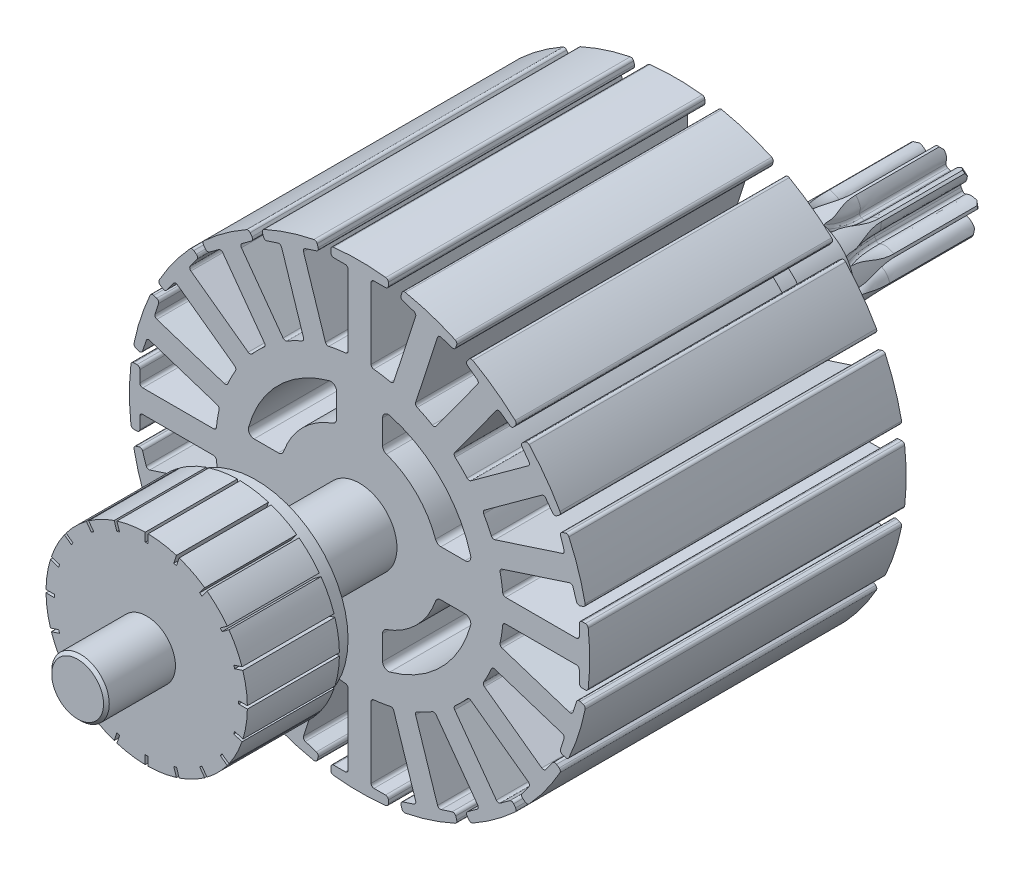
SolidWorks part; units mm, degrees
ref_plane "Plan de face" through (0, 0, 0) normal (0, 0, 1) x (1, 0, 0)
ref_plane "Plan de dessus" through (0, 0, 0) normal (0, 1, 0) x (1, 0, 0)
ref_plane "Plan de droite" through (0, 0, 0) normal (1, 0, 0) x (0, 0, -1)
sketch "Esquisse1" plane through (0, 0, 0) normal (0, 0, 1) x (1, 0, 0)
  line L0 (0, 0) -> (0, 10.3983) construction
  line L1 (0, 0) -> (3.7078, 10.1871) construction
  line L2 (0, 0) -> (2.253, 11.5906) construction
  line L3 (0, 0) -> (-2.0231, 10.408) construction
  line L4 (0, 0) -> (1.8345, 11.5827) construction
  line L5 (0, 0) -> (-4.42, 12.1438) construction
  line L6 (1.4536, 3.9937) -> (0, 0)
  line L7 (0, 0) -> (-1.4536, 3.9937)
  arc A0 (0.2448, 6.9957) -> (-0.2448, 6.9957) centre (0, 0) ccw
  arc A1 (-1.2344, 4.0668) -> (-1.4536, 3.9937) centre (0, 0) ccw
  circle A2 centre (0, 0) radius 6.3725 construction
  arc A3 (0.88, 4.5271) -> (1.2344, 4.0668) centre (1.3796, 4.5452) ccw
  arc A4 (-0.88, 4.5271) -> (-1.2344, 4.0668) centre (-1.3796, 4.5452) cw
  arc A29 (1.4536, 3.9937) -> (1.2344, 4.0668) centre (0, 0) ccw
  circle A37 centre (0, 0) radius 6 construction
  spline S0 degree 3 poles (0.2448, 6.9957) (0.4073, 6.7815) (0.7899, 6.277) (1.1774, 5.4103) (0.8723, 4.7372) (0.88, 4.5271) knots 0 0 0 0 0.240722 0.567033 0.793625 0.793625 0.793625 0.793625
  spline S1 degree 3 poles (-0.2448, 6.9957) (-0.4011, 6.7811) (-0.7955, 6.2397) (-1.0968, 5.3828) (-0.9392, 4.6977) (-0.88, 4.5271) knots 0 0 0 0 0.237443 0.59898 0.793625 0.793625 0.793625 0.793625
  dimension "D1" = 14
  dimension "D2" = 8.5
  dimension "D7" = 0.5
  dimension "D8" = 12
  dimension "D3" = 20
  dimension "D4" = 11
  dimension "D5" = 11
  dimension "D6" = 2
  dimension "D9" = 20
extrude "Extrusion1" add sketch "Esquisse1" along normal blind 15
sketch "Esquisse3" plane through (0, 0, 15) normal (0, 0, 1) x (1, 0, 0)
  circle A0 centre (0, 0) radius 7
  dimension "D1" = 14
extrude "Extrusion3" add sketch "Esquisse3" along normal blind 17
pattern_circular "Répétition circulaire4" count 9 over 360 about axis through (0, 0, 15) along (0, 0, -1) of "Extrusion1"
sketch "Esquisse5" plane through (0, 0, 15) normal (0, 0, -1) x (-1, 0, 0)
  line L0 (-2.1626, -6.6576) -> (-2.1626, -10.0208)
  line L1 (-2.1626, -10.0208) -> (2.1626, -10.0208)
  line L2 (2.1626, -10.0208) -> (2.1626, -6.6576)
  line L3 (-3.9207, -15.5978) -> (4.8254, -15.5978) construction
  arc A4 (-2.1626, -6.6576) -> (2.1626, -6.6576) centre (0, 0) ccw
  arc A5 (0.7214, -4.555) -> (0.2309, -4.2437) centre (0.2581, -4.743) ccw
  arc A6 (-0.2309, -4.2437) -> (0.2309, -4.2437) centre (0, 0) ccw
  arc A7 (-0.2309, -4.2437) -> (-0.7214, -4.555) centre (-0.2581, -4.743) ccw
  arc A9 (0.7214, -4.555) -> (0.2309, -4.2437) centre (0.2581, -4.743) ccw
  arc A10 (-0.2309, -4.2437) -> (0.2309, -4.2437) centre (0, 0) ccw
  arc A11 (-0.2309, -4.2437) -> (-0.7214, -4.555) centre (-0.2581, -4.743) ccw
  spline S2 degree 3 poles (3886.3041, -3149.0802) (-64.6229, 43.1927) (4.3207, -0.2579) (-12.6625, -17.7913) (-61.6142, 59.0529) (1886.4899, -4635.8009) knots -6.085701 -6.085701 -6.085701 -6.085701 0.226592 0.552903 14.320818 14.320818 14.320818 14.320818 only from (-0.7214, -4.555) to (-2.1626, -6.6576)
  spline S3 degree 3 poles (-3024.547, -3985.8721) (82.1896, 50.0108) (10.7712, -17.5704) (-4.5054, 1.0438) (53.4936, 49.2721) (-493.2688, -4979.5142) knots -12.92515 -12.92515 -12.92515 -12.92515 0.237443 0.59898 8.114893 8.114893 8.114893 8.114893 only from (2.1626, -6.6576) to (0.7214, -4.555)
  spline S4 degree 3 poles (-0.7214, -4.555) (-0.8005, -4.7498) (-0.7441, -5.4867) (-1.4046, -6.1686) (-1.9367, -6.5118) (-2.1626, -6.6576) knots 0 0 0 0 0.226592 0.552903 0.793625 0.793625 0.793625 0.793625
  spline S5 degree 3 poles (2.1626, -6.6576) (1.9423, -6.5093) (1.3866, -6.1355) (0.8104, -5.4333) (0.7242, -4.7356) (0.7214, -4.555) knots 0 0 0 0 0.237443 0.59898 0.793625 0.793625 0.793625 0.793625
  dimension "D1" = 0
revolve "Enlèvement de matière-Révolution1" cut sketch "Esquisse5" angle 360 about L3
pattern_circular "Répétition circulaire1" count 9 over 360 of "Enlèvement de matière-Révolution1"
chamfer "Chanfrein1" distance 0.5 angle 45 9 edges at (0, 7, 0) (-4.4995, 5.3623, 0) (-6.8937, 1.2155, 0) (-6.0622, -3.5, 0) (-2.3941, -6.5778, 0) (2.3941, -6.5778, 0) (6.0622, -3.5, 0) (6.8937, 1.2155, 0) (4.4995, 5.3623, 0)
sketch "Esquisse6" plane through (0, 0, 32) normal (0, 0, 1) x (1, 0, 0)
  circle A0 centre (0, 0) radius 9
  dimension "D1" = 18
extrude "Extrusion4" add sketch "Esquisse6" along normal blind 14
sketch "Esquisse15" plane through (0, 0, 32) normal (0, 0, -1) x (-1, 0, 0)
  circle A0 centre (0, 0) radius 7
  circle A1 centre (0, 0) radius 7.5
  dimension "D1" = 15
  dimension "D2" = 14
extrude "Extrusion11" add sketch "Esquisse15" along normal blind 9 from offset 0.5
sketch "Esquisse7" plane through (0, 0, 46) normal (0, 0, 1) x (1, 0, 0)
  circle A0 centre (0, 0) radius 6.5
  dimension "D1" = 13
extrude "Extrusion5" add sketch "Esquisse7" along normal blind 92
sketch "Esquisse8" plane through (0, 0, 138) normal (0, 0, 1) x (1, 0, 0)
  circle A0 centre (0, 0) radius 5
  dimension "D1" = 10
extrude "Extrusion6" add sketch "Esquisse8" along normal blind 12
chamfer "Chanfrein2" distance 0.5 angle 45 1 edges at (5, 0, 150)
sketch "Esquisse9" plane through (0, 0, 0) normal (0, 1, 0) x (1, 0, 0)
  line L0 (0, -149.5) -> (0, -138) construction
  line L1 (4.8, -140.5) -> (6.1083, -140.5)
  line L2 (4.8, -140.5) -> (4.8, -141.5)
  line L3 (4.8, -141.5) -> (6.1083, -141.5)
  line L4 (6.1083, -140.5) -> (6.1083, -141.5)
  line L5 (-4.5, -150) -> (4.5, -150) construction
  dimension "D1" = 4.8
  dimension "D2" = 1
  dimension "D3" = 8.5
revolve "Enlèvement de matière-Révolution2" [suppressed] cut sketch "Esquisse9" angle 360
sketch "Esquisse10" plane through (0, 0, 46) normal (0, 0, 1) x (1, 0, 0)
  circle A0 centre (0, 0) radius 25
  dimension "D1" = 50
extrude "Extrusion7" add sketch "Esquisse10" along normal blind 55
sketch "Esquisse11" plane through (0, 0, 46) normal (0, 0, -1) x (-1, 0, 0)
  line L0 (0, 0) -> (0, 30.4129) construction
  line L1 (0, 0) -> (27.2746, 0) construction
  line L2 (4, 18.3303) -> (4, 14.1421)
  line L3 (14.1421, 4) -> (18.3303, 4)
  arc A0 (13.1993, 4.6667) -> (4.6667, 13.1993) centre (0, 0) ccw
  arc A1 (19.2951, 5.2632) -> (5.2632, 19.2951) centre (0, 0) ccw
  arc A2 (4, 18.3303) -> (5.2632, 19.2951) centre (5, 18.3303) cw
  arc A3 (4, 14.1421) -> (4.6667, 13.1993) centre (5, 14.1421) ccw
  arc A4 (14.1421, 4) -> (13.1993, 4.6667) centre (14.1421, 5) cw
  arc A5 (18.3303, 4) -> (19.2951, 5.2632) centre (18.3303, 5) ccw
  dimension "D5" = 1
  dimension "D3" = 4
  dimension "D4" = 4
extrude "Enlèv. mat.-Extru.1" cut sketch "Esquisse11" against normal through all
pattern_circular "Répétition circulaire5" count 4 over 360 about axis through (0, 0, 101) along (0, 0, -1) of "Enlèv. mat.-Extru.1"
sketch "Esquisse12" plane through (0, 0, 46) normal (0, 0, -1) x (-1, 0, 0)
  line L0 (0, 0) -> (0, 43.5367) construction
  line L1 (5, 39.6863) -> (5, 38.1863)
  line L2 (5, 38.1863) -> (2, 38.1863)
  line L3 (2, 38.1863) -> (2, 24.9199)
  line L4 (-2, 38.1863) -> (-2, 24.9199)
  line L5 (-5, 38.1863) -> (-2, 38.1863)
  line L6 (-5, 39.6863) -> (-5, 38.1863)
  arc A1 (5, 39.6863) -> (-5, 39.6863) centre (0, 0) ccw
  arc A2 (2, 24.9199) -> (-2, 24.9199) centre (0, 0) ccw
  dimension "D1" = 50
  dimension "D5" = 40
  dimension "D2" = 4
  dimension "D3" = 10
  dimension "D4" = 1.5
extrude "Extrusion8" add sketch "Esquisse12" against normal up to surface (55 mm away) up to face at (-10.693, -10.693, 101)
fillet "Congé1" radius 0.5 8 edges at (-2, 38.1863, 73.5) (-2, 24.9199, 73.5) (-5, 38.1863, 73.5) (-5, 39.6863, 73.5) (2, 24.9199, 73.5) (2, 38.1863, 73.5) (5, 38.1863, 73.5) (5, 39.6863, 73.5)
pattern_circular "Répétition circulaire2" count 20 over 360 about axis through (0, 0, 138) along (0, 0, -1) of "Congé1", "Extrusion8"
sketch "Esquisse13" plane through (0, 0, 138) normal (0, 0, 1) x (1, 0, 0)
  circle A0 centre (0, 0) radius 6.5
  circle A1 centre (0, 0) radius 16
  dimension "D1" = 32
extrude "Extrusion9" add sketch "Esquisse13" against normal blind 19
sketch "Esquisse14" plane through (0, 0, 138) normal (0, 0, 1) x (1, 0, 0)
  line L0 (0, 0) -> (0, 18.654) construction
  line L1 (0, 0) -> (-5.8062, 17.8696) construction
  line L2 (-0.25, 17.4982) -> (-0.25, 15.9932)
  line L3 (-5.1695, 16.719) -> (-4.7044, 15.2877)
  arc A0 (-0.25, 15.9932) -> (-4.7044, 15.2877) centre (0, 0) ccw
  arc A1 (-0.25, 17.4982) -> (-5.1695, 16.719) centre (0, 0) ccw
  dimension "D1" = 35
  dimension "D5" = 15.9951
  dimension "D2" = 18
  dimension "D3" = 0.5
  dimension "D4" = 0.5
extrude "Extrusion10" add sketch "Esquisse14" against normal blind 16
pattern_circular "Répétition circulaire3" count 20 over 360 about axis through (0, 0, 119) along (0, 0, 1) of "Extrusion10"
